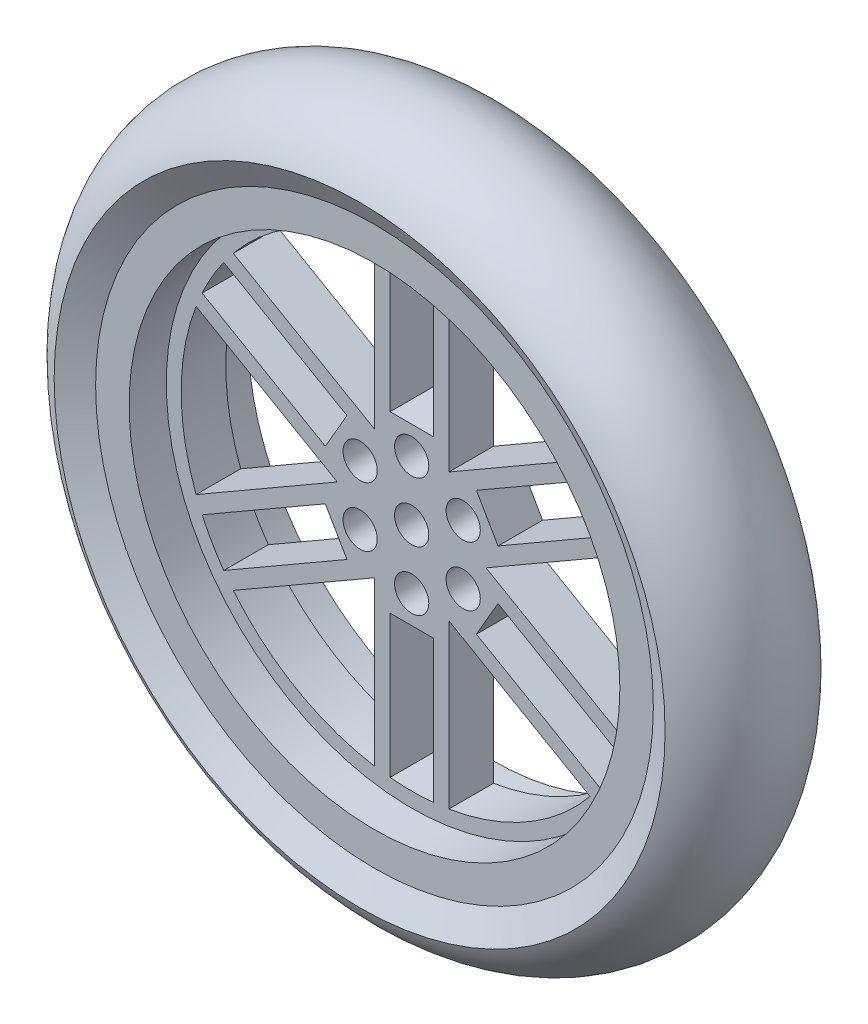
SolidWorks part; units mm, degrees
ref_plane "前视基准面" through (0, 0, 0) normal (0, 0, 1) x (1, 0, 0)
ref_plane "上视基准面" through (0, 0, 0) normal (0, 1, 0) x (1, 0, 0)
ref_plane "右视基准面" through (0, 0, 0) normal (1, 0, 0) x (0, 0, -1)
sketch "草图1" plane through (0, 0, 0) normal (1, 0, 0) x (0, 0, -1)
  line L0 (-10, 0) -> (-10, 48.4758) construction
  line L1 (-8, 37.5052) -> (8, 37.5052)
  line L2 (-10, 41.0826) -> (-8, 37.5052)
  line L3 (8, 37.5052) -> (10, 41.0826)
  line L4 (10, 0) -> (10, 62.3456) construction
  line L5 (-8, 0) -> (-8, 6.7861) construction
  line L6 (8, 0) -> (8, 6.2479) construction
  arc A0 (10, 41.0826) -> (-10, 41.0826) centre (0, 36.5) ccw
  point P1 (10, 0)
  point P2 (0, 47.5)
  point P3 (0, 47.5)
  point P6 (-10, 0)
  point P7 (-10, 41.0826)
  point P14 (8, 0)
  point P18 (-8, 0)
ref_axis "基准轴1" through (0, 0, 15.4) along (0, 0, -1)
revolve "旋转1" add sketch "草图1" angle 360 about axis through (0, 0, 15.4) along (0, 0, -1)
sketch "草图2" plane through (0, 0, 0) normal (0, 0, 1) x (1, 0, 0)
  line L0 (0, 0) -> (0, 31) construction
  line L1 (0, 0) -> (26.8468, 15.5) construction
  line L2 (5, 30.5941) -> (5, 8.6603)
  line L3 (5, 8.6603) -> (23.9953, 19.6272)
  line L4 (10, 0) -> (28.9953, -10.9669)
  line L5 (28.9953, 10.9669) -> (10, 0)
  line L6 (5, -8.6603) -> (5, -30.5941)
  line L7 (23.9953, -19.6272) -> (5, -8.6603)
  line L8 (-5, -8.6603) -> (-23.9953, -19.6272)
  line L9 (-5, -30.5941) -> (-5, -8.6603)
  line L10 (-10, 0) -> (-28.9953, 10.9669)
  line L11 (-28.9953, -10.9669) -> (-10, 0)
  line L12 (-5, 8.6603) -> (-5, 30.5941)
  line L13 (-23.9953, 19.6272) -> (-5, 8.6603)
  line L40 (-2.9047, 30.8636) -> (-2.9047, 11.729)
  line L41 (-2.9047, 11.729) -> (2.9047, 11.729)
  line L43 (2.9047, 11.729) -> (2.9047, 30.8636)
  line L45 (8.7053, 8.3801) -> (11.61, 3.349)
  line L47 (11.61, 3.349) -> (28.181, 12.9163)
  line L49 (25.2763, 17.9474) -> (8.7053, 8.3801)
  line L52 (11.61, -3.349) -> (8.7053, -8.3801)
  line L53 (8.7053, -8.3801) -> (25.2763, -17.9474)
  line L54 (28.181, -12.9163) -> (11.61, -3.349)
  line L57 (2.9047, -11.729) -> (-2.9047, -11.729)
  line L58 (-2.9047, -11.729) -> (-2.9047, -30.8636)
  line L59 (2.9047, -30.8636) -> (2.9047, -11.729)
  line L60 (-8.7053, -8.3801) -> (-11.61, -3.349)
  line L61 (-11.61, -3.349) -> (-28.181, -12.9163)
  line L62 (-25.2763, -17.9474) -> (-8.7053, -8.3801)
  line L63 (-11.61, 3.349) -> (-8.7053, 8.3801)
  line L64 (-8.7053, 8.3801) -> (-25.2763, 17.9474)
  line L65 (-28.181, 12.9163) -> (-11.61, 3.349)
  circle A1 centre (0, 0) radius 2.3
  circle A2 centre (0, 0) radius 37.5052 construction
  circle A3 centre (0, 0) radius 37.5052
  circle A4 centre (0, 8) radius 2.3
  circle A5 centre (6.9282, 4) radius 2.3
  circle A6 centre (6.9282, -4) radius 2.3
  circle A7 centre (0, -8) radius 2.3
  circle A8 centre (-6.9282, -4) radius 2.3
  circle A9 centre (-6.9282, 4) radius 2.3
  circle A11 centre (0, 0) radius 10 construction
  arc A17 (-5, 30.5941) -> (-23.9953, 19.6272) centre (0, 0) ccw
  arc A18 (-25.2763, 17.9474) -> (-28.181, 12.9163) centre (0, 0) ccw
  arc A19 (-28.9953, 10.9669) -> (-28.9953, -10.9669) centre (0, 0) ccw
  arc A20 (2.9047, 30.8636) -> (-2.9047, 30.8636) centre (0, 0) ccw
  arc A21 (28.181, 12.9163) -> (25.2763, 17.9474) centre (0, 0) ccw
  arc A22 (23.9953, 19.6272) -> (5, 30.5941) centre (0, 0) ccw
  arc A23 (25.2763, -17.9474) -> (28.181, -12.9163) centre (0, 0) ccw
  arc A24 (28.9953, -10.9669) -> (28.9953, 10.9669) centre (0, 0) ccw
  arc A25 (-23.9953, -19.6272) -> (-5, -30.5941) centre (0, 0) ccw
  arc A26 (-28.181, -12.9163) -> (-25.2763, -17.9474) centre (0, 0) ccw
  arc A27 (-2.9047, -30.8636) -> (2.9047, -30.8636) centre (0, 0) ccw
  arc A28 (5, -30.5941) -> (23.9953, -19.6272) centre (0, 0) ccw
  point P19 (0, 0)
  point P43 (0, 0)
  point P67 (0, 0)
  point P69 (0, 0)
  dimension "D1" = 6
  dimension "D2" = 6
  dimension "D3" = 6
extrude "凸台-拉伸2" add sketch "草图2" along normal mid plane 16 separate body
sketch "草图3" plane through (0, 0, 8) normal (0, 0, 1) x (1, 0, 0)
  circle A0 centre (0, 0) radius 33
extrude "切除-拉伸1" cut sketch "草图3" against normal blind 5
extrude "切除-拉伸2" cut sketch "草图3<2>" along normal blind 5 from surface starting at face at (-18.4727, -10.6652, -8)
sketch "草图3<2>" plane through (0, 0, 8) normal (0, 0, 1) x (1, 0, 0) same geometry as "草图3"
